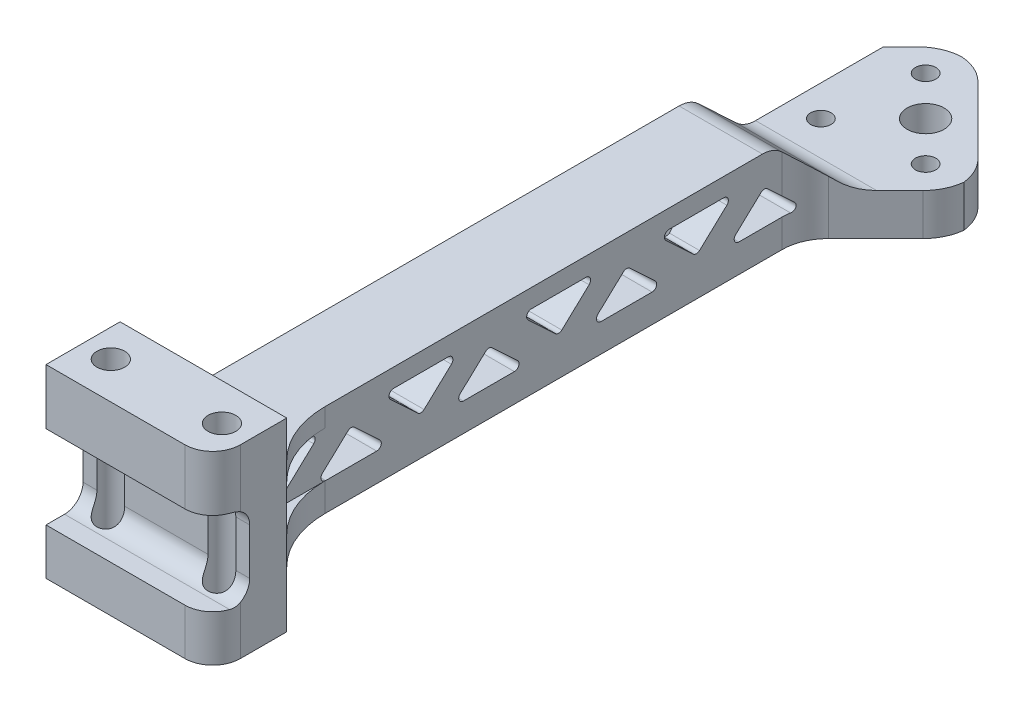
SolidWorks part; units mm, degrees
ref_plane "Front Plane" through (0, 0, 0) normal (0, 0, 1) x (1, 0, 0)
ref_plane "Top Plane" through (0, 0, 0) normal (0, 1, 0) x (1, 0, 0)
ref_plane "Right Plane" through (0, 0, 0) normal (1, 0, 0) x (0, 0, -1)
sketch "Sketch2" plane through (0, 0, 0) normal (0, 1, 0) x (1, 0, 0)
  line L0 (0, 90.435) -> (0, 0)
  line L1 (0, 0) -> (15, 0)
  line L2 (18, 3) -> (18, 8)
  line L3 (18, 8) -> (11.9289, 14.0711)
  line L4 (9, 21.1421) -> (9, 72.565)
  line L5 (9, 72.565) -> (9, 86) construction
  line L6 (3, 4) -> (15, 4) construction
  line L7 (0, 90.435) -> (3.3076, 93.7426)
  line L8 (3.3076, 93.7426) -> (6.9142, 93.7426)
  line L9 (6.9142, 93.7426) -> (17.0459, 83.6109)
  line L10 (17.0459, 83.6109) -> (17.0459, 80.6109)
  line L11 (17.0459, 80.6109) -> (9, 72.565)
  line L12 (9, 86) -> (13.2426, 81.7574) construction
  line L13 (3.3431, 80.3431) -> (9, 86) construction
  line L14 (9, 86) -> (4.7574, 90.2426) construction
  circle A0 centre (9, 86) radius 6 construction
  circle A1 centre (9, 86) radius 8 construction
  circle A2 centre (3, 4) radius 1.5
  circle A3 centre (15, 4) radius 1.5
  arc A4 (18, 3) -> (15, 0) centre (15, 3) cw
  circle A6 centre (13.2426, 81.7574) radius 1.1
  circle A7 centre (3.3431, 80.3431) radius 1.1
  circle A8 centre (4.7574, 90.2426) radius 1.1
  circle A9 centre (9, 86) radius 2
  arc A10 (11.9289, 14.0711) -> (9, 21.1421) centre (19, 21.1421) cw
  point P16 (18, 0)
  dimension "D9" = 3
  dimension "D10" = 3
  dimension "D12" = 12
  dimension "D13" = 16
  dimension "D18" = 2.2
  dimension "D19" = 4
  dimension "D25" = 10
  dimension "D1" = 18
  dimension "D2" = 8
  dimension "D3" = 12
  dimension "D4" = 4
  dimension "D5" = 3
  dimension "D6" = 3
  dimension "D7" = 45
  dimension "D8" = 9
  dimension "D11" = 82
  dimension "D14" = 45
  dimension "D15" = 90
  dimension "D16" = 90
  dimension "D17" = 3.5
  dimension "D20" = 3.5
  dimension "D21" = 45
  dimension "D22" = 3.5
  dimension "D23" = 4
  dimension "D24" = 3
extrude "Boss-Extrude1" add sketch "Sketch2" along normal blind 10
sketch "Sketch3" plane through (0, 0, 0) normal (-1, 0, 0) x (0, 0, 1)
  line L0 (-93.7426, 8) -> (3.8778, 8) construction
  line L1 (-93.7426, 10) -> (-93.7426, 0) construction
  line L2 (3.8778, 8) -> (3.8778, 6.8085) construction
  line L3 (3.8778, 6.8085) -> (-93.7426, 6.8085) construction
  line L4 (-93.7426, 6.8085) -> (-93.7426, 5) construction
  line L5 (-93.7426, 5) -> (3.6815, 5) construction
  line L6 (3.6815, 5) -> (3.6815, 4.0586) construction
  line L7 (3.6815, 4.0586) -> (-96.3247, 4.0586) construction
  line L8 (-96.3247, 4.0586) -> (-96.3247, 3.0503) construction
  line L9 (-96.3247, 3.0503) -> (3.8778, 3.0503) construction
  line L12 (-8, 8) -> (-8, 3.0503)
  line L13 (-8, 3.0503) -> (-13.3, 3.0503)
  line L14 (-13.3, 3.0503) -> (-8, 8)
  line L15 (-12.3953, 8) -> (-16.6157, 4.0586)
  line L16 (-16.6157, 4.0586) -> (-20.8361, 8)
  line L17 (-20.8361, 8) -> (-12.3953, 8)
  line L18 (-19.9315, 3.0503) -> (-23.9556, 6.8085)
  line L19 (-23.9556, 6.8085) -> (-27.9798, 3.0503)
  line L20 (-27.9798, 3.0503) -> (-19.9315, 3.0503)
  line L21 (-35.7111, 8) -> (-27.2703, 8)
  line L22 (-31.4907, 4.0586) -> (-35.7111, 8)
  line L23 (-27.2703, 8) -> (-31.4907, 4.0586)
  line L24 (-50.5861, 8) -> (-42.1453, 8)
  line L25 (-46.3657, 4.0586) -> (-50.5861, 8)
  line L26 (-42.1453, 8) -> (-46.3657, 4.0586)
  line L27 (-65.461, 8) -> (-57.0202, 8)
  line L28 (-61.2406, 4.0586) -> (-65.461, 8)
  line L29 (-57.0202, 8) -> (-61.2406, 4.0586)
  line L30 (-34.8065, 3.0503) -> (-38.8306, 6.8085)
  line L31 (-38.8306, 6.8085) -> (-42.8547, 3.0503)
  line L32 (-42.8547, 3.0503) -> (-34.8065, 3.0503)
  line L33 (-108.6176, 5) -> (-11.1934, 5) construction
  line L34 (-49.6814, 3.0503) -> (-53.7056, 6.8085)
  line L35 (-53.7056, 6.8085) -> (-57.7297, 3.0503)
  line L36 (-57.7297, 3.0503) -> (-49.6814, 3.0503)
  line L37 (-123.4926, 5) -> (-26.0684, 5) construction
  line L38 (-64.5564, 3.0503) -> (-68.5805, 6.8085)
  line L39 (-68.5805, 6.8085) -> (-72.6047, 3.0503)
  line L40 (-72.6047, 3.0503) -> (-64.5564, 3.0503)
  line L41 (-138.3675, 5) -> (-40.9434, 5) construction
  line L42 (-77, 8) -> (-77, 3.0503)
  line L43 (-77, 3.0503) -> (-71.7, 8)
  line L44 (-71.7, 8) -> (-77, 8)
  line L45 (0, 10) -> (0, 0) construction
  point P56 (-70.5926, 4.9294)
  dimension "D2" = 3
  dimension "D7" = 5.3
  dimension "D8" = 3
  dimension "D9" = 3
  dimension "D12" = 8
  dimension "D13" = 77
  dimension "D14" = 3
  dimension "D15" = 3.1332
  dimension "D10" = 4
  dimension "D11" = 4
extrude "Cut-Extrude2" cut sketch "Sketch3" against normal up to next
sketch "Sketch4" plane through (9, 0, 0) normal (1, 0, 0) x (0, 0, -1)
  line L1 (8, 8) -> (21.1421, 8)
  line L2 (8, 8) -> (8, 3.0503)
  line L3 (8, 3.0503) -> (21.1421, 3.0503)
  line L4 (21.1421, 8) -> (21.1421, 3.0503)
extrude "Cut-Extrude3" cut sketch "Sketch4" along normal blind 30
sketch "Sketch5" plane through (0, 10, 0) normal (0, 1, 0) x (1, 0, 0)
  line L0 (18, 8) -> (0, 8)
  line L1 (0, 90.435) -> (0, 0) construction
  line L2 (0, 8) -> (0, 0)
  line L3 (0, 0) -> (15, 0)
  line L4 (18, 3) -> (18, 8) construction
  line L5 (18, 3) -> (18, 8)
  circle A0 centre (15, 4) radius 1.5 construction
  circle A1 centre (15, 4) radius 1.5
  arc A2 (15, 0) -> (18, 3) centre (15, 3) ccw construction
  circle A3 centre (3, 4) radius 1.5 construction
  circle A4 centre (3, 4) radius 1.5
  arc A5 (15, 0) -> (18, 3) centre (15, 3) ccw
extrude "Boss-Extrude2" add sketch "Sketch5" along normal blind 10
fillet "Fillet1" radius 0.5 4 edges at (4.5, 4.0586, -61.2406) (4.5, 4.0586, -46.3657) (4.5, 4.0586, -31.4907) (4.5, 4.0586, -16.6157)
fillet "Fillet2" radius 0.5 5 edges at (6.7175, 8, -77) (4.5, 8, -65.461) (4.5, 8, -50.5861) (4.5, 8, -35.7111) (4.5, 8, -20.8361)
fillet "Fillet3" radius 0.5 5 edges at (4.5, 8, -71.7) (4.5, 8, -57.0202) (4.5, 8, -42.1453) (4.5, 8, -27.2703) (4.5, 8, -12.3953)
fillet "Fillet4" radius 0.5 1 edges at (6.7175, 3.0503, -77)
fillet "Fillet5" radius 0.5 4 edges at (4.5, 3.0503, -27.9798) (4.5, 3.0503, -42.8547) (4.5, 3.0503, -57.7297) (4.5198, 3.0503, -72.6047)
fillet "Fillet6" radius 0.5 4 edges at (4.5, 3.0503, -19.9315) (4.5, 3.0503, -34.8065) (4.5, 3.0503, -49.6814) (4.5, 3.0503, -64.5564)
fillet "Fillet7" radius 0.5 4 edges at (4.5, 6.8085, -68.5805) (4.5, 6.8085, -53.7056) (4.5, 6.8085, -38.8306) (4.5, 6.8085, -23.9556)
sketch "Sketch6" plane through (0, 0, 0) normal (-1, 0, 0) x (0, 0, 1)
  line L0 (0, 20) -> (0, 0) construction
  line L1 (0, 14) -> (-4, 14)
  line L2 (0, 14) -> (0, 5)
  line L3 (0, 5) -> (-4, 5)
  line L4 (-4, 14) -> (-4, 5)
  line L5 (-90.435, 0) -> (0, 0) construction
  line L6 (-8, 20) -> (0, 20) construction
  dimension "D1" = 5
  dimension "D2" = 6
  dimension "D3" = 4
extrude "Cut-Extrude4" cut sketch "Sketch6" against normal through all
sketch "Sketch7" plane through (0, 0, 0) normal (-1, 0, 0) x (0, 0, 1)
  line L0 (-8, 20) -> (-8, 10)
  line L1 (-8, 20) -> (-8, 10) construction
  line L2 (-8, 10) -> (-18, 10)
  line L3 (-90.435, 10) -> (-8, 10) construction
  line L4 (-18, 10) -> (-8, 20)
  line L5 (-8, 20) -> (0, 20) construction
  point P5 (-8, 20)
  dimension "D1" = 45
extrude "Boss-Extrude3" add sketch "Sketch7" against normal blind 10
sketch "Sketch8" plane through (0, 0, 0) normal (-1, 0, 0) x (0, 0, 1)
  line L0 (-76.1587, 3.836) -> (-72.6267, 7.1346) construction
  line L1 (-72.9679, 8) -> (-76.5, 8) construction
  line L2 (-77, 7.5) -> (-77, 4.2014) construction
  line L3 (-77, 7.5) -> (-77, 4.2014)
  line L4 (-72.9679, 8) -> (-76.5, 8)
  line L5 (-76.1587, 3.836) -> (-72.6267, 7.1346)
  arc A0 (-72.6267, 7.1346) -> (-72.9679, 8) centre (-72.9679, 7.5) ccw construction
  arc A1 (-77, 4.2014) -> (-76.1587, 3.836) centre (-76.5, 4.2014) ccw construction
  arc A2 (-76.5, 8) -> (-77, 7.5) centre (-76.5, 7.5) ccw construction
  arc A3 (-76.5, 8) -> (-77, 7.5) centre (-76.5, 7.5) ccw
  arc A4 (-77, 4.2014) -> (-76.1587, 3.836) centre (-76.5, 4.2014) ccw
  arc A5 (-72.6267, 7.1346) -> (-72.9679, 8) centre (-72.9679, 7.5) ccw
  point P5 (-72.5028, 7.6834)
  point P14 (-76.6992, 3.7428)
extrude "Boss-Extrude4" add sketch "Sketch8" against normal up to surface (12.5938 mm away) up to face at (11.7627, 6.1289, -75.3277)
sketch "Sketch9" plane through (0, 0, 0) normal (-1, 0, 0) x (0, 0, 1)
  line L0 (-69.5584, 10) -> (-75.4477, 4.5)
  line L1 (-90.435, 10) -> (-18, 10) construction
  line L2 (-75.4477, 4.5) -> (-96.8521, 4.5)
  line L3 (-96.8521, 4.5) -> (-96.8521, 10)
  line L4 (-96.8521, 10) -> (-69.5584, 10)
  line L5 (-68.9218, 6.4898) -> (-71.678, 3.9157) construction
  line L6 (-90.435, 0) -> (0, 0) construction
  dimension "D1" = 3
  dimension "D2" = 4.5
extrude "Cut-Extrude5" cut sketch "Sketch9" against normal through all
fillet "Fillet8" radius 2 1 edges at (9, 5, -4)
fillet "Fillet9" radius 2 1 edges at (9, 14, -4)
chamfer "Chamfer1" distance 7 angle 50 1 edges at (10, 15, -13) first distance on face at (10, 12.5, -12.6958)
fillet "Fillet10" radius 2 3 edges at (14, 10, -8) (5.8289, 10, -13.0503) (5.8289, 15.0503, -8)
fillet "Fillet11" radius 3 2 edges at (5.9414, 4.5, -75.4477) (4.5, 10, -69.5584)
fillet "Fillet12" radius 5 5 edges at (3.3076, 2.25, -93.7426) (6.9142, 2.25, -93.7426) (17.0459, 2.25, -83.6109) (17.0459, 2.25, -80.6109) (9, 3.5961, -72.565)
sketch "Sketch10" plane through (0, 0, 0) normal (0, -1, 0) x (1, 0, 0)
  line L0 (0, -90.435) -> (0, 0) construction
  circle A0 centre (4.5, -61.5855) radius 1.25
  dimension "D1" = 2.5
  dimension "D2" = 4.5
  dimension "D3" = 32.15
extrude "Cut-Extrude6" cut sketch "Sketch10" against normal blind 6
